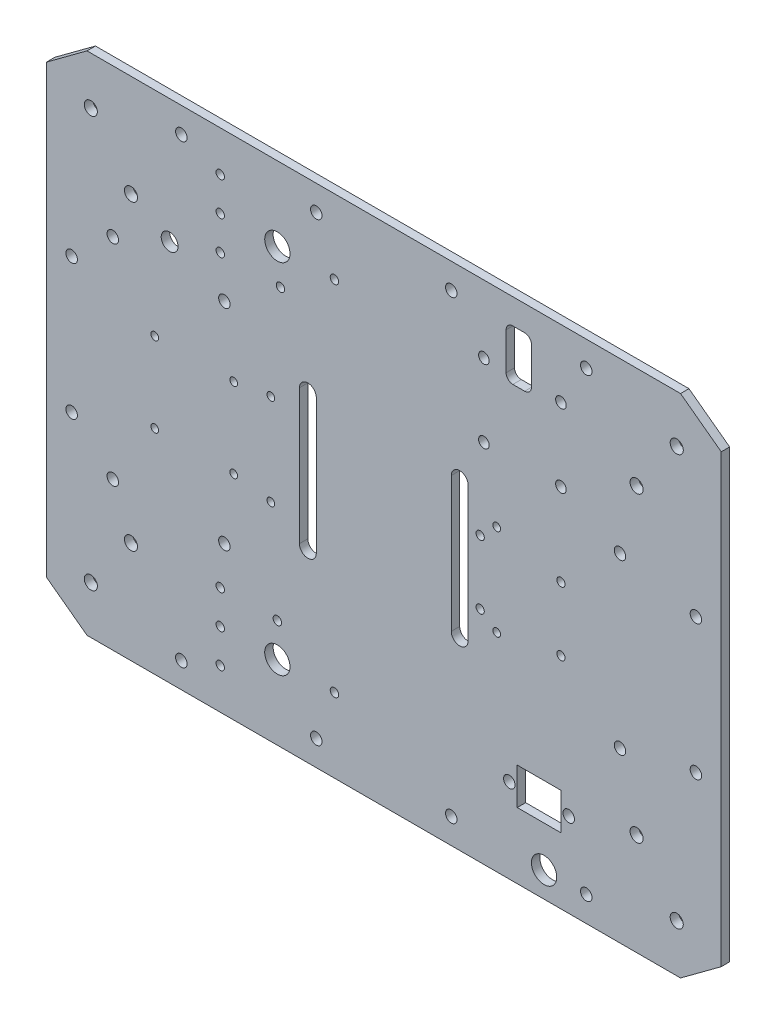
SolidWorks part; units mm, degrees
material "Thornel Mat VMA"
ref_plane "Front Plane" through (0, 0, 0) normal (0, 0, 1) x (1, 0, 0)
ref_plane "Top Plane" through (0, 0, 0) normal (0, 1, 0) x (1, 0, 0)
ref_plane "Right Plane" through (0, 0, 0) normal (1, 0, 0) x (0, 0, -1)
sketch "Sketch1" plane through (0, 0, 0) normal (0, 0, 1) x (1, 0, 0)
  line L0 (-127, 0) -> (127, 0) construction
  line L1 (0, -95.25) -> (0, 95.25) construction
  line L2 (-107.95, 0) -> (-107.95, 41.011) construction
  line L3 (-107.95, 41.011) -> (-95.25, 41.011) construction
  line L4 (-95.25, 41.011) -> (-79.9365, 52.3423) construction
  line L5 (-79.9365, 52.3423) -> (-79.9365, 76.2) construction
  line L6 (-79.9365, 76.2) -> (0, 76.2) construction
  line L7 (-95.25, 41.011) -> (-127, 83.9186) construction
  line L8 (-79.9365, 52.3423) -> (-111.6865, 95.25) construction
  line L9 (-111.6865, -95.25) -> (-127, -83.9186)
  line L10 (111.6865, -95.25) -> (127, -83.9186)
  line L11 (111.6865, 95.25) -> (127, 83.9186)
  line L12 (-87.5933, 46.6767) -> (-95.1475, 56.8856) construction
  line L13 (-95.1475, 56.8856) -> (-110.256, 77.3036) construction
  line L24 (127, -83.9186) -> (127, 83.9186)
  line L26 (111.6865, 95.25) -> (-111.6865, 95.25)
  line L27 (-111.6865, 95.25) -> (-127, 83.9186)
  line L28 (-127, 83.9186) -> (-127, -83.9186)
  line L30 (-111.6865, -95.25) -> (111.6865, -95.25)
  circle A0 centre (-95.1475, 56.8856) radius 2.4638
  circle A1 centre (-110.256, 77.3036) radius 2.4638
  circle A2 centre (110.256, 77.3036) radius 2.4638
  circle A3 centre (95.1475, 56.8856) radius 2.4638
  circle A4 centre (-110.256, -77.3036) radius 2.4638
  circle A5 centre (-95.1475, -56.8856) radius 2.4638
  circle A6 centre (110.256, -77.3036) radius 2.4638
  circle A7 centre (95.1475, -56.8856) radius 2.4638
  point P12 (0, 0)
  dimension "D1" = 190.5
  dimension "D2" = 254
  dimension "D3" = 19.05
  dimension "D4" = 19.05
  dimension "D5" = 12.7
  dimension "D6" = 19.05
  dimension "D7" = 143.5
  dimension "D8" = 12.7
  dimension "D9" = 25.4
extrude "Boss-Extrude1" add sketch "Sketch1" along normal blind 3.175
sketch "Sketch2" plane through (0, 0, 3.175) normal (0, 0, 1) x (1, 0, 0)
  line L0 (-127, 0) -> (127, 0) construction
  line L1 (-127, 83.9186) -> (-127, -83.9186) construction
  line L2 (127, -83.9186) -> (127, 83.9186) construction
  line L3 (-111.6865, -95.25) -> (111.6865, -95.25) construction
  line L4 (127, -83.9186) -> (127, 83.9186) construction
  line L13 (50.2285, -70.4215) -> (66.6115, -70.4215)
  line L14 (50.2285, -70.4215) -> (50.2285, -56.5785)
  line L15 (50.2285, -56.5785) -> (66.6115, -56.5785)
  line L16 (66.6115, -70.4215) -> (66.6115, -56.5785)
  line L17 (50.2285, -70.4215) -> (66.6115, -56.5785) construction
  line L18 (50.2285, -56.5785) -> (66.6115, -70.4215) construction
  circle A4 centre (69.596, -63.5) radius 2.159
  circle A5 centre (47.244, -63.5) radius 2.159
  point P6 (0, 0)
  point P7 (0, 0)
  point P8 (0, 0)
  point P9 (47.0169, -63.6524)
  point P10 (33.399, -63.6524)
  point P15 (69.596, -63.5)
  point P16 (47.244, -63.5)
  point P17 (69.596, -63.5)
  point P18 (58.42, -63.5)
  point P25 (58.42, -63.5)
  point P36 (0, 0)
  point P37 (99.4433, -2.9683)
  point P38 (100.5634, -0.4917)
  point P39 (0, 0)
  point P40 (0, 0)
  point P41 (70.9036, -13.3817)
  point P42 (0, 0)
  dimension "D6" = 13.843
  dimension "D8" = 11.176
  dimension "D1" = 11.176
  dimension "D2" = 31.75
  dimension "D3" = 68.58
  dimension "D7" = 16.383
extrude "Cut-Extrude1" cut sketch "Sketch2" against normal through all contours L13 L16 L15 L14 | A5 | A4 region at (58.42, -63.5, 3.175) region at (69.596, -63.5, 3.175) region at (47.244, -63.5, 3.175)
sketch "Sketch3" plane through (0, 0, 3.175) normal (0, 0, 1) x (1, 0, 0)
  line L0 (0, 95.25) -> (0, -95.25) construction
  line L1 (111.6865, 95.25) -> (-111.6865, 95.25) construction
  line L2 (-111.6865, -95.25) -> (111.6865, -95.25) construction
  line L3 (127, 0) -> (-127, 0) construction
  line L4 (127, -83.9186) -> (127, 83.9186) construction
  line L5 (-127, 83.9186) -> (-127, -83.9186) construction
  line L8 (119.3433, -89.5843) -> (111.789, -79.3753) construction
  line L10 (111.6865, -95.25) -> (127, -83.9186) construction
  line L11 (111.6865, -95.25) -> (127, -83.9186)
  circle A0 centre (111.789, -79.3753) radius 1.9844
  circle A1 centre (96.6805, -58.9574) radius 1.9844
  dimension "D2" = 3.9688
  dimension "D3" = 3.9688
  dimension "D1" = 12.7
  dimension "D4" = 25.4
sketch "Sketch5" plane through (0, 0, 0) normal (0, 0, -1) x (-1, 0, 0)
  line L0 (-127, 0) -> (127, 0) construction
  line L1 (105.9946, 43.5) -> (55.9947, 43.5) construction
  line L2 (105.9946, 43.5) -> (105.9946, -43.5) construction
  line L3 (105.9946, -43.5) -> (55.9947, -43.5) construction
  line L4 (55.9947, 43.5) -> (55.9947, -43.5) construction
  line L5 (89.4966, 18.0341) -> (89.4966, -18.0339)
  line L6 (67.8946, 95.25) -> (67.8946, -95.25) construction
  line L7 (111.6865, -95.25) -> (-111.6865, -95.25) construction
  line L8 (0, 64.0679) -> (0, -49.8393) construction
  line L9 (-42.5, 17.2) -> (42.5, 17.2) construction
  line L10 (-42.5, 17.2) -> (-42.5, -17.2) construction
  line L11 (-42.5, -17.2) -> (42.5, -17.2) construction
  line L12 (42.5, 17.2) -> (42.5, -17.2) construction
  line L13 (-42.5, 17.2) -> (42.5, -17.2) construction
  line L14 (-42.5, -17.2) -> (42.5, 17.2) construction
  line L15 (46.8402, 60.96) -> (31.75, 60.96) construction
  line L16 (61.5446, -67.31) -> (-87.4336, -67.31) construction
  line L17 (-127, -83.9186) -> (-127, 83.9186) construction
  line L18 (40.0554, 67.31) -> (18.5661, 67.31) construction
  line L19 (-28.575, 25.4) -> (-28.575, -25.4) construction
  line L21 (-127, -83.9186) -> (-127, 83.9186) construction
  line L22 (-50.8, 76.2) -> (80.5946, 76.2) construction
  line L23 (80.5946, 76.2) -> (80.5946, 48.58) construction
  line L25 (80.5946, -77.0458) -> (80.5946, 48.58) construction
  line L26 (127, 0) -> (-127, 0) construction
  line L27 (80.9947, 0) -> (80.9947, -8419.0368) construction
  line L28 (-25.4, 25.4) -> (-25.4, -25.4)
  line L29 (-31.75, 25.4) -> (-31.75, -25.4)
  line L30 (28.575, 25.4) -> (28.575, -25.4) construction
  line L31 (25.4, 25.4) -> (25.4, -25.4)
  line L32 (31.75, 25.4) -> (31.75, -25.4)
  line L33 (71.3384, 0) -> (71.3384, 12.3782) construction
  line L34 (53.4794, 18.0341) -> (89.4966, 18.0341)
  line L35 (53.4794, 18.0341) -> (53.4794, -18.0339)
  line L36 (53.4794, -18.0339) -> (89.4966, -18.0339)
  line L37 (-46.0375, 66.675) -> (-55.5625, 66.675)
  line L38 (-46.0375, 66.675) -> (-46.0375, 85.725)
  line L39 (-46.0375, 85.725) -> (-55.5625, 85.725)
  line L40 (-50.8, 76.2) -> (-50.8, 95.25) construction
  line L41 (-55.5625, 66.675) -> (-55.5625, 85.725)
  line L42 (-46.0375, 66.675) -> (-55.5625, 85.725) construction
  line L43 (-46.0375, 85.725) -> (-55.5625, 66.675) construction
  line L47 (-127, -83.9186) -> (-127, 83.9186) construction
  line L48 (-111.6865, 95.25) -> (111.6865, 95.25) construction
  circle A0 centre (61.5446, -54.61) radius 1.5875
  circle A1 centre (61.5446, -67.31) radius 1.5875
  circle A2 centre (80.5946, 48.58) radius 3.175
  circle A3 centre (-60.325, -85.725) radius 4.7625
  circle A4 centre (61.5446, 54.61) radius 1.5875
  circle A5 centre (61.5446, -80.01) radius 1.5875
  circle A7 centre (40.0554, -67.31) radius 4.7625
  circle A8 centre (61.5446, 67.31) radius 1.5875
  circle A9 centre (61.5446, 80.01) radius 1.5875
  circle A10 centre (40.0554, 67.31) radius 4.7625
  circle A12 centre (59.9952, 39.4995) radius 2.159
  circle A13 centre (101.9941, 39.4995) radius 2.159
  circle A14 centre (59.9952, -39.4995) radius 2.159
  circle A15 centre (101.9941, -39.4995) radius 2.159
  circle A16 centre (18.5661, 67.31) radius 1.5875
  circle A17 centre (38.8861, 54.61) radius 1.5875
  circle A18 centre (18.5661, -67.31) radius 1.5875
  circle A19 centre (40.0554, -54.61) radius 1.5875
  arc A20 (-25.4, 25.4) -> (-31.75, 25.4) centre (-28.575, 25.4) ccw
  arc A21 (-31.75, -25.4) -> (-25.4, -25.4) centre (-28.575, -25.4) ccw
  arc A22 (25.4, 25.4) -> (31.75, 25.4) centre (28.575, 25.4) cw
  arc A23 (31.75, -25.4) -> (25.4, -25.4) centre (28.575, -25.4) cw
  circle A24 centre (56.4794, 15.0341) radius 1.4478
  circle A25 centre (56.4794, -15.0341) radius 1.4478
  circle A26 centre (86.1974, -15.0341) radius 1.4478
  circle A27 centre (86.1974, 15.0341) radius 1.4478
  circle A28 centre (-42.5, 17.2) radius 1.4542
  circle A29 centre (-42.5, -17.2) radius 1.4541
  circle A30 centre (42.5, -17.2) radius 1.4541
  circle A31 centre (42.5, 17.2) radius 1.4542
  point P0 (80.9947, 0)
  point P9 (0, 0)
  point P77 (-28.575, 0)
  point P84 (28.575, 0)
  point P89 (71.3384, 0)
  dimension "D10" = 6.35
  dimension "D15" = 2.9997
  dimension "D17" = 66.675
  dimension "D22" = 76.2
  dimension "D25" = 4.0005
  dimension "D45" = 2.8956
  dimension "D9" = 9.525
  dimension "D13" = 14.859
  dimension "D14" = 3
  dimension "D20" = 9.525
  dimension "D8" = 9.525
  dimension "D19" = 19.05
  dimension "D16" = 9.525
  dimension "D1" = 87.0001
  dimension "D2" = 49.9999
  dimension "D4" = 34.4
  dimension "D5" = 85
  dimension "D6" = 6.35
  dimension "D7" = 12.7
  dimension "D11" = 5.08
  dimension "D12" = 25.4
  dimension "D24" = 19.05
  dimension "D26" = 4.0005
  dimension "D38" = 50.8
  dimension "D39" = 6.35
  dimension "D40" = 28.575
  dimension "D41" = 36.0172
  dimension "D42" = 36.068
  dimension "D44" = 3
extrude "Cut-Extrude2" cut sketch "Sketch5" against normal through all contours A2 | A14 | A15 | A13 | A12 | L29 A21 L28 A20 | A23 L4 A22 L31 | A23 L32 A22 L4 | A27 | A24 | A25 | A26
sketch "Sketch6" plane through (0, 0, 0) normal (0, 0, -1) x (-1, 0, 0)
  line L0 (0, 0) -> (-135.1326, 0) construction
  line L1 (0, 0) -> (0, -95.25) construction
  line L2 (111.6865, -95.25) -> (-111.6865, -95.25) construction
  line L3 (-76.2, -95.25) -> (-76.2, -85.725) construction
  line L4 (117.475, 0) -> (117.475, -25.4) construction
  line L5 (127, 0) -> (-127, 0) construction
  line L6 (127, 83.9186) -> (127, -83.9186) construction
  circle A0 centre (-76.2, -85.725) radius 2.159
  circle A1 centre (-25.4, -85.725) radius 2.159
  circle A2 centre (25.4, -85.725) radius 2.159
  circle A3 centre (76.2, -85.725) radius 2.159
  circle A4 centre (76.2, 85.725) radius 2.159
  circle A5 centre (25.4, 85.725) radius 2.159
  circle A6 centre (-25.4, 85.725) radius 2.159
  circle A7 centre (-76.2, 85.725) radius 2.159
  circle A8 centre (117.475, -25.4) radius 2.159
  circle A9 centre (117.475, 25.4) radius 2.159
  circle A10 centre (-117.475, 25.4) radius 2.159
  circle A11 centre (-117.475, -25.4) radius 2.159
  dimension "D2" = 9.525
  dimension "D3" = 76.2
  dimension "D5" = 9.525
  dimension "D6" = 25.4
  dimension "D4" = 4
extrude "Cut-Extrude3" cut sketch "Sketch6" against normal through all
extrude "Cut-Extrude4" cut sketch "Sketch5<3>" against normal through all contours A28 | A29 | A31 | A30
sketch "Sketch5<3>" plane through (0, 0, 0) normal (0, 0, -1) x (-1, 0, 0) same geometry as "Sketch5"
extrude "Cut-Extrude5" cut sketch "Sketch5<4>" against normal through all contours A3 | A10 | A9 | A8 | A4 | A0 | A1 | A5 | A7 region at (60.325, -85.725, 0)
sketch "Sketch5<4>" plane through (0, 0, 0) normal (0, 0, -1) x (-1, 0, 0) same geometry as "Sketch5"
extrude "Cut-Extrude6" cut sketch "Sketch5<5>" against normal blind 2.54 contours A18 | A17 | A16
sketch "Sketch5<5>" plane through (0, 0, 0) normal (0, 0, -1) x (-1, 0, 0) same geometry as "Sketch5"
extrude "Cut-Extrude7" cut sketch "Sketch5<6>" against normal through all contours A17 | A18 | A16
sketch "Sketch5<6>" plane through (0, 0, 0) normal (0, 0, -1) x (-1, 0, 0) same geometry as "Sketch5"
extrude "Cut-Extrude8" cut sketch "Sketch5<7>" against normal blind 2.54 and the other way blind 7.62 contours L41 L37 L38 L39 | A19
sketch "Sketch5<7>" plane through (0, 0, 0) normal (0, 0, -1) x (-1, 0, 0) same geometry as "Sketch5"
extrude "Cut-Extrude9" cut sketch "Sketch5<9>" against normal through all contours A19
sketch "Sketch5<9>" plane through (0, 0, 0) normal (0, 0, -1) x (-1, 0, 0) same geometry as "Sketch5"
extrude "Cut-Extrude17" cut sketch "Sketch5<15>" against normal through all both and the other way through all contours L39 L41 L37 L38
sketch "Sketch5<15>" plane through (0, 0, 0) normal (0, 0, -1) x (-1, 0, 0) same geometry as "Sketch5"
fillet "Fillet1" radius 2.54 1 edges at (55.5625, 85.725, 1.5875) type face fillet first side face at (55.5625, 76.2, 1.5875) second side face at (50.8, 85.725, 1.5875)
fillet "Fillet2" radius 2.54 1 edges at (46.0375, 85.725, 1.5875) type face fillet first side face at (49.53, 85.725, 1.5875) second side face at (46.0375, 76.2, 1.5875)
fillet "Fillet3" radius 2.54 1 edges at (46.0375, 66.675, 1.5875) type face fillet first side face at (50.8, 66.675, 1.5875) second side face at (46.0375, 74.93, 1.5875)
fillet "Fillet4" radius 2.54 1 edges at (55.5625, 66.675, 1.5875) type face fillet first side face at (52.07, 66.675, 1.5875) second side face at (55.5625, 74.93, 1.5875)
sketch "Sketch9" plane through (0, 0, 3.175) normal (0, 0, 1) x (1, 0, 0)
  line L0 (127, -83.9186) -> (127, 83.9186) construction
  line L1 (36.275, 11.3) -> (66.675, 11.3) construction
  line L2 (36.275, 11.3) -> (36.275, -12.7) construction
  line L3 (36.275, -12.7) -> (66.675, -12.7) construction
  line L4 (66.675, 11.3) -> (66.675, -12.7) construction
  line L5 (-111.6865, -95.25) -> (111.6865, -95.25) construction
  line L6 (127, -83.9186) -> (127, 83.9186) construction
  line L7 (66.675, 69.85) -> (37.675, 69.85) construction
  line L8 (66.675, 69.85) -> (66.675, 42.35) construction
  line L9 (66.675, 42.35) -> (37.675, 42.35) construction
  line L10 (37.675, 69.85) -> (37.675, 42.35) construction
  line L11 (111.6865, 95.25) -> (-111.6865, 95.25) construction
  line L12 (127, 0) -> (0, 0) construction
  line L13 (88.9, 34.925) -> (88.9, -34.925) construction
  line L14 (95.25, 34.925) -> (82.55, 34.925) construction
  line L15 (95.25, 34.925) -> (95.25, -34.925) construction
  line L16 (95.25, -34.925) -> (82.55, -34.925) construction
  line L17 (82.55, 34.925) -> (82.55, -34.925) construction
  line L18 (95.25, 0) -> (82.55, 0) construction
  circle A0 centre (36.275, 11.3) radius 1.55
  circle A1 centre (66.675, 11.3) radius 1.55
  circle A2 centre (66.675, -12.7) radius 1.55
  circle A3 centre (36.275, -12.7) radius 1.55
  circle A4 centre (66.675, 69.85) radius 2
  circle A5 centre (37.675, 69.85) radius 2
  circle A6 centre (37.675, 42.35) radius 2
  circle A7 centre (66.675, 42.35) radius 2
  circle A8 centre (88.9, 31.75) radius 2.159
  circle A9 centre (88.9, -31.75) radius 2.159
  point P40 (88.9, 0)
  point P41 (95.25, 26.1318)
  dimension "D1" = 3.1
  dimension "D6" = 4
  dimension "D11" = 4.318
  dimension "D12" = 3.175
  dimension "D13" = 12.7
  dimension "D2" = 24
  dimension "D3" = 30.4
  dimension "D4" = 60.325
  dimension "D5" = 82.55
  dimension "D7" = 29
  dimension "D8" = 27.5
  dimension "D9" = 60.325
  dimension "D10" = 25.4
  dimension "D14" = 38.1
  dimension "D15" = 63.5
extrude "Cut-Extrude18" cut sketch "Sketch9" against normal through all
